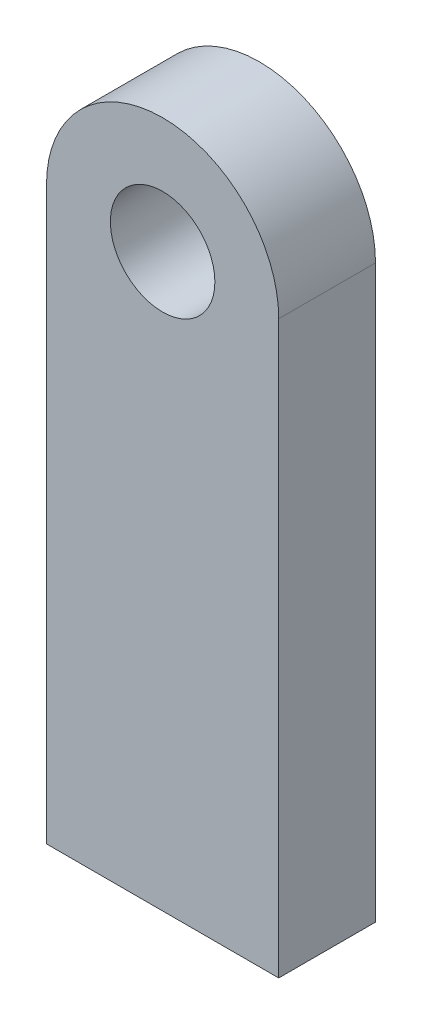
SolidWorks part; units mm, degrees
ref_plane "Front Plane" through (0, 0, 0) normal (0, 0, 1) x (1, 0, 0)
ref_plane "Top Plane" through (0, 0, 0) normal (0, 1, 0) x (1, 0, 0)
ref_plane "Right Plane" through (0, 0, 0) normal (1, 0, 0) x (0, 0, -1)
sketch "Sketch1" plane through (0, 0, 0) normal (0, 0, 1) x (1, 0, 0)
  line L1 (0, 0) -> (15.24, 0)
  line L2 (0, 0) -> (0, 37.465)
  line L3 (0, 37.465) -> (15.24, 37.465)
  line L4 (15.24, 0) -> (15.24, 37.465)
  arc A0 (0, 37.465) -> (15.24, 37.465) centre (7.62, 37.465) cw
  circle A1 centre (7.62, 37.465) radius 3.429
  dimension "D2" = 6.858
  dimension "D1" = 37.465
  dimension "D3" = 15.24
extrude "Boss-Extrude1" add sketch "Sketch1" along normal blind 6.35 contours A1 L3 L2 L1 L4 | A1 L3 A0 region at (7.62, 18.1549, 0) region at (7.62, 41.1507, 0)
